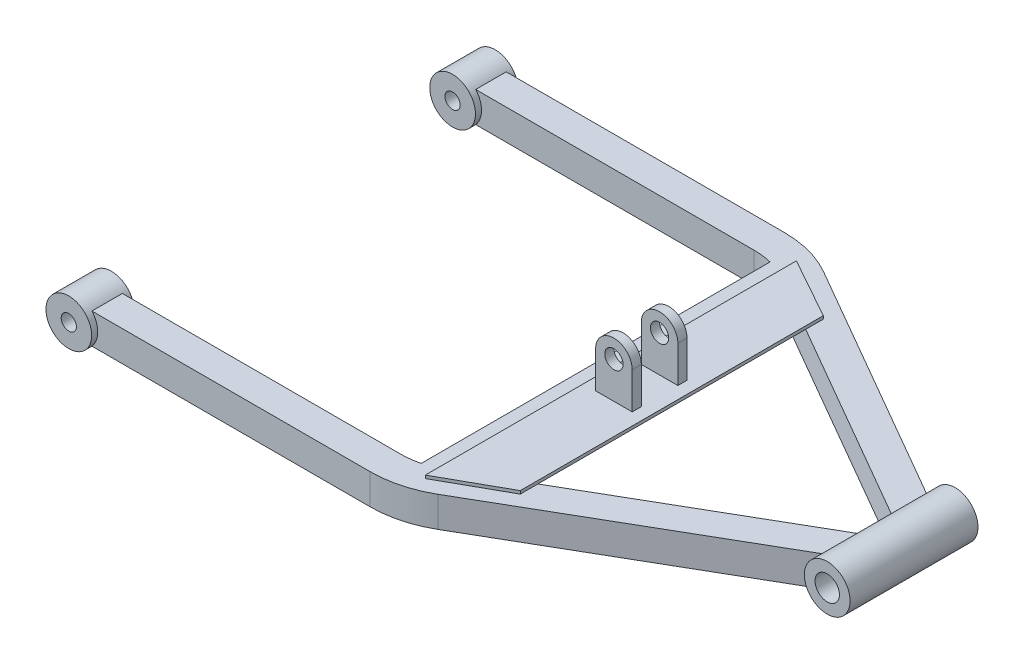
SolidWorks part; units mm, degrees
material "1060 Alloy"
ref_plane "Front Plane" through (0, 0, 0) normal (0, 0, 1) x (1, 0, 0)
ref_plane "Top Plane" through (0, 0, 0) normal (0, 1, 0) x (1, 0, 0)
ref_plane "Right Plane" through (0, 0, 0) normal (1, 0, 0) x (0, 0, -1)
sketch "Sketch1" plane through (0, 0, 0) normal (0, 1, 0) x (1, 0, 0)
  line L0 (0, 0) -> (200, 0) construction
  line L1 (0, 63) -> (96.9615, 63)
  line L2 (111.9615, 58.9808) -> (200, 8.1517)
  arc A0 (96.9615, 63) -> (111.9615, 58.9808) centre (96.9615, 33) cw
  point P8 (105, 63)
  dimension "D5" = 30
  dimension "D1" = 200
  dimension "D2" = 105
  dimension "D3" = 63
  dimension "D4" = 150
ref_plane "Plane1" through (0, 0, -63) normal (0, 0, 1) x (1, 0, 0)
sketch "Sketch2" plane through (0, 0, -63) normal (0, 0, 1) x (1, 0, 0)
  circle A0 centre (0, 0) radius 7.5
  circle A1 centre (0, 0) radius 2.5
  dimension "D1" = 15
  dimension "D2" = 5
extrude "Boss-Extrude1" add sketch "Sketch2" along normal mid plane 14
ref_plane "Plane2" through (0, 0, -63) normal (1, 0, 0) x (0, 0, -1)
sketch "Sketch3" plane through (0, 0, -63) normal (1, 0, 0) x (0, 0, -1)
  line L1 (-5, -5) -> (5, -5)
  line L2 (-5, -5) -> (-5, 5)
  line L3 (-5, 5) -> (5, 5)
  line L4 (5, -5) -> (5, 5)
  line L5 (-5, -5) -> (5, 5) construction
  line L6 (-5, 5) -> (5, -5) construction
  point P0 (0, 0)
  dimension "D1" = 10
sketch "Sketch4" plane through (0, 0, 0) normal (0, 0, 1) x (1, 0, 0)
  line L0 (111.9615, 0) -> (200, 0) construction
  circle A0 centre (200, 0) radius 7.5
  circle A1 centre (200, 0) radius 4
  dimension "D1" = 8
  dimension "D2" = 15
extrude "Boss-Extrude2" add sketch "Sketch4" along normal mid plane 42 separate body
sweep "Sweep1" add profiles "Sketch3" path "Sketch1"
mirror "Mirror1" about plane through (0, 0, 0) normal (0, 0, 1) of "Sweep1", "Boss-Extrude1"
extrude "Cut-Extrude1" cut sketch "Sketch2<2>" along normal blind 137 and the other way blind 20 contours A1 region at (0, 0, -63)
sketch "Sketch2<2>" plane through (0, 0, -63) normal (0, 0, 1) x (1, 0, 0) same geometry as "Sketch2"
extrude "Cut-Extrude2" cut sketch "Sketch4<2>" against normal mid plane 60 contours A1 region at (200, 0, 0)
sketch "Sketch4<2>" plane through (0, 0, 0) normal (0, 0, 1) x (1, 0, 0) same geometry as "Sketch4"
sketch "Sketch5" plane through (0, 0, 0) normal (0, 0, 1) x (1, 0, 0)
  line L0 (114.4615, 5) -> (96.9615, 5) construction
  line L1 (102.9615, -5) -> (112.9615, -5)
  line L2 (102.9615, -5) -> (102.9615, 5)
  line L3 (102.9615, 5) -> (112.9615, 5)
  line L4 (112.9615, -5) -> (112.9615, 5)
  line L5 (102.9615, -5) -> (112.9615, 5) construction
  line L6 (102.9615, 5) -> (112.9615, -5) construction
  line L7 (96.9615, -5) -> (96.9615, 5) construction
  point P0 (107.9615, 0)
  dimension "D1" = 10
  dimension "D2" = 10
  dimension "D3" = 11
extrude "Boss-Extrude3" add sketch "Sketch5" along normal up to next and the other way up to next
sketch "Sketch6" plane through (0, 5, 0) normal (0, 1, 0) x (1, 0, 0)
  line L0 (102.9615, 0) -> (112.9615, 0) construction
  line L1 (102.9615, 57.2693) -> (102.9615, -57.2693) construction
  line L2 (112.9615, 52.6299) -> (112.9615, -52.6299) construction
  line L3 (107.9615, 60.9106) -> (107.9615, -60.9106)
  line L4 (107.9615, 60.9106) -> (127.9615, 49.7432)
  line L5 (111.9615, 58.9808) -> (200, 8.1517) construction
  line L6 (127.9615, 49.7432) -> (127.9615, -49.7432)
  line L7 (127.9615, -49.7432) -> (107.9615, -60.9106)
  arc A0 (111.9615, 58.9808) -> (96.9615, 63) centre (96.9615, 33) ccw construction
  point P8 (107.9615, 0)
  dimension "D1" = 20
extrude "Boss-Extrude4" add sketch "Sketch6" along normal blind 1
sketch "Sketch7" plane through (0, 0, 0) normal (0, 0, 1) x (1, 0, 0)
  line L0 (111.9615, 6) -> (111.9615, 18)
  line L1 (107.9615, 6) -> (127.9615, 6) construction
  line L2 (123.9615, 18) -> (123.9615, 6)
  line L3 (111.9615, 6) -> (123.9615, 6)
  arc A0 (111.9615, 18) -> (123.9615, 18) centre (117.9615, 18) cw
  circle A1 centre (117.9615, 18) radius 3
  dimension "D1" = 6
  dimension "D4" = 6
  dimension "D2" = 12
  dimension "D3" = 10
extrude "Boss-Extrude5" add sketch "Sketch7" along normal blind 3 from offset 6
mirror "Mirror2" about plane through (0, 0, 0) normal (0, 0, 1) of "Boss-Extrude5"
equation "\"D3@Sketch1\"=126/2"
